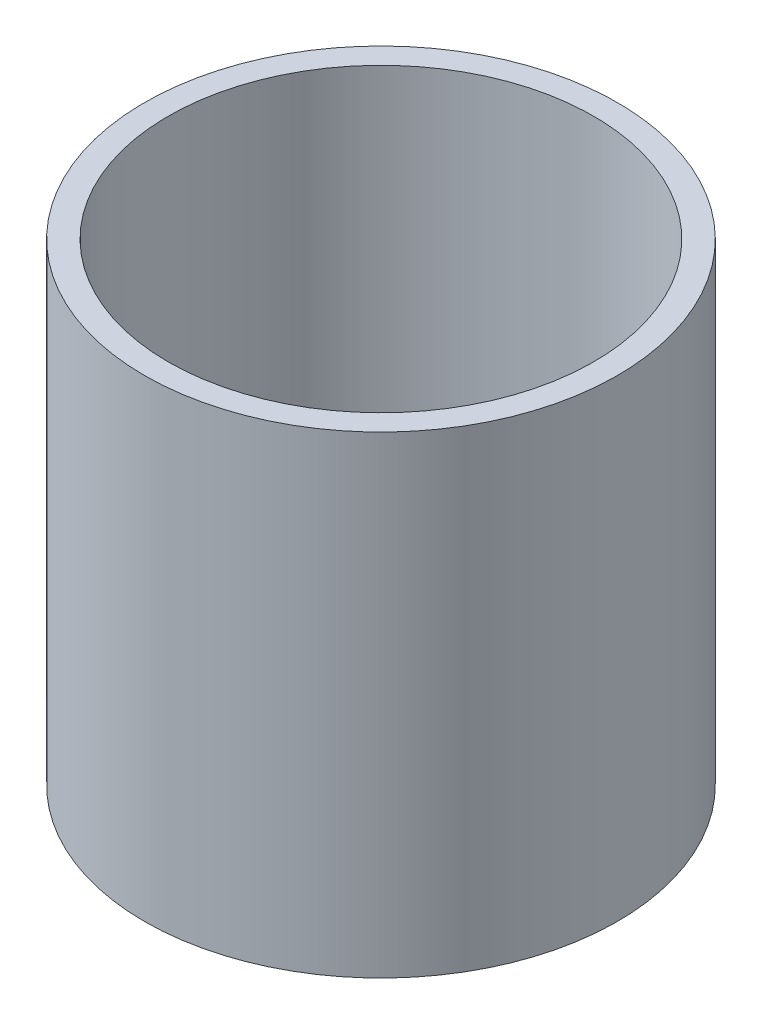
SolidWorks part; units mm, degrees
ref_plane "Front Plane" through (0, 0, 0) normal (0, 0, 1) x (1, 0, 0)
ref_plane "Top Plane" through (0, 0, 0) normal (0, 1, 0) x (1, 0, 0)
ref_plane "Right Plane" through (0, 0, 0) normal (1, 0, 0) x (0, 0, -1)
sketch "Sketch1" plane through (0, 0, 0) normal (0, 1, 0) x (1, 0, 0)
  circle A0 centre (0, 0) radius 1250
  circle A1 centre (0, 0) radius 1125
  circle A2 centre (0, 0) radius 1187.5 construction
  dimension "D1" = 2250
  dimension "D2" = 2500
  dimension "D3" = 2375
extrude "Boss-Extrude1" add sketch "Sketch1" along normal blind 2500
